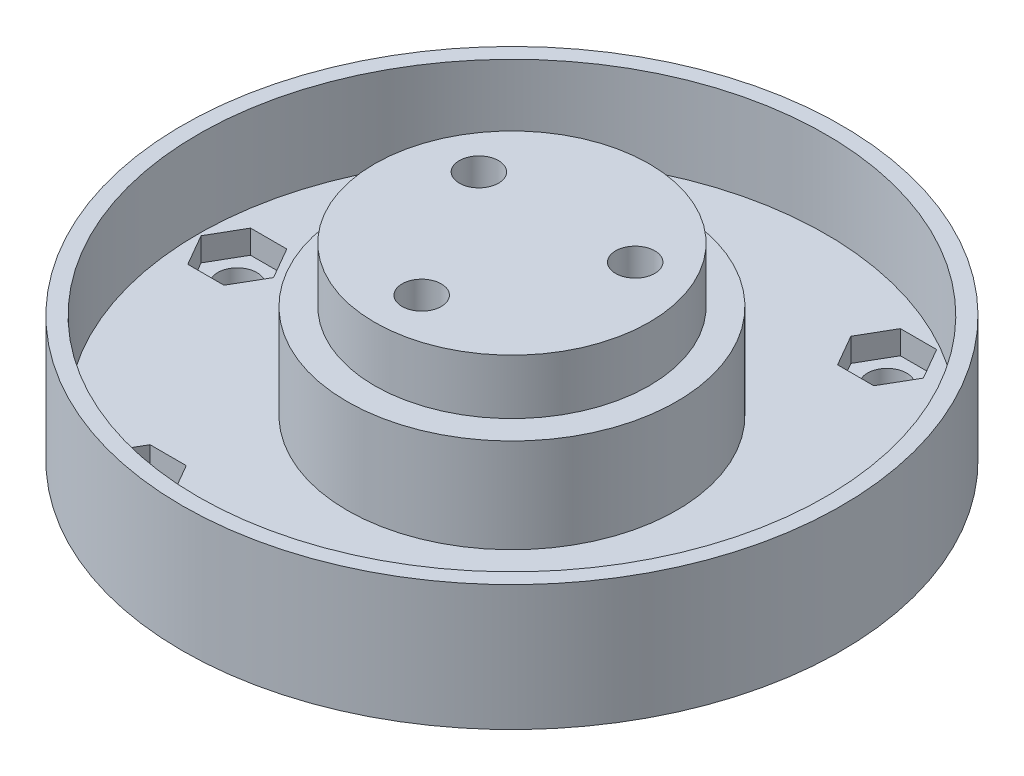
SolidWorks part; units mm, degrees
ref_plane "Front Plane" through (0, 0, 0) normal (0, 0, 1) x (1, 0, 0)
ref_plane "Top Plane" through (0, 0, 0) normal (0, 1, 0) x (1, 0, 0)
ref_plane "Right Plane" through (0, 0, 0) normal (1, 0, 0) x (0, 0, -1)
sketch "Sketch1" plane through (0, 0, 0) normal (0, 1, 0) x (1, 0, 0)
  line L0 (0, 0) -> (0, -11.5) construction
  line L1 (0, 0) -> (9.9593, 5.75) construction
  line L2 (0, 0) -> (-9.9593, 5.75) construction
  circle A0 centre (0, 0) radius 42
  circle A1 centre (0, 0) radius 21
  circle A2 centre (0, 0) radius 17.5
  circle A3 centre (0, 0) radius 40
  circle A4 centre (-9.9593, 5.75) radius 2.5
  circle A5 centre (9.9593, 5.75) radius 2.5
  circle A6 centre (0, -11.5) radius 2.5
  dimension "D1" = 35
  dimension "D2" = 42
  dimension "D3" = 2
  dimension "D6" = 5
  dimension "D8" = 80
  dimension "D4" = 120
  dimension "D5" = 120
  dimension "D7" = 11.5
extrude "Boss-Extrude1" add sketch "Sketch1" along normal blind 24 contours A2 region at (0, 0, 0)
extrude "Boss-Extrude2" add sketch "Sketch1<3>" along normal blind 17 contours A1 A2 region at (-20.406, 0, 0)
sketch "Sketch1<3>" plane through (0, 0, 0) normal (0, 1, 0) x (1, 0, 0) same geometry as "Sketch1"
extrude "Boss-Extrude4" add sketch "Sketch1<6>" along normal blind 5 contours A3 A1 region at (-38.8686, 0, 0)
sketch "Sketch1<6>" plane through (0, 0, 0) normal (0, 1, 0) x (1, 0, 0) same geometry as "Sketch1"
extrude "Boss-Extrude5" add sketch "Sketch1<7>" along normal blind 16 contours A0 A3 region at (-40.8121, 0, 0)
sketch "Sketch1<7>" plane through (0, 0, 0) normal (0, 1, 0) x (1, 0, 0) same geometry as "Sketch1"
sketch "Sketch2" plane through (0, 5, 0) normal (0, 1, 0) x (1, 0, 0)
  line L0 (0, 0) -> (-42, 0) construction
  circle A0 centre (0, 0) radius 30 construction
  circle A1 centre (0, 0) radius 35 construction
  circle A2 centre (-35, 0) radius 2.5
  circle A3 centre (-17.5, 30.3109) radius 2.5
  circle A4 centre (0, 0) radius 42 construction
  circle A5 centre (17.5, 30.3109) radius 2.5
  circle A6 centre (35, 0) radius 2.5
  circle A7 centre (17.5, -30.3109) radius 2.5
  circle A8 centre (-17.5, -30.3109) radius 2.5
  point P22 (0, 0)
  dimension "D1" = 60
  dimension "D2" = 5
  dimension "D3" = 5
  dimension "D4" = 6
extrude "Cut-Extrude1" cut sketch "Sketch2" against normal through all
sketch "Sketch3" plane through (0, 5, 0) normal (0, 1, 0) x (1, 0, 0)
  line L0 (0, 0) -> (0, 42) construction
  line L1 (-12.8812, 30.3109) -> (-15.1906, 34.3109)
  line L2 (-15.1906, 34.3109) -> (-19.8094, 34.3109)
  line L3 (-19.8094, 34.3109) -> (-22.1188, 30.3109)
  line L4 (-22.1188, 30.3109) -> (-19.8094, 26.3109)
  line L5 (-19.8094, 26.3109) -> (-15.1906, 26.3109)
  line L6 (-15.1906, 26.3109) -> (-12.8812, 30.3109)
  line L7 (0, 0) -> (36.3731, 21) construction
  line L8 (19.8094, 26.3109) -> (22.1188, 30.3109)
  line L9 (22.1188, 30.3109) -> (19.8094, 34.3109)
  line L10 (19.8094, 34.3109) -> (15.1906, 34.3109)
  line L11 (15.1906, 34.3109) -> (12.8812, 30.3109)
  line L12 (12.8812, 30.3109) -> (15.1906, 26.3109)
  line L13 (15.1906, 26.3109) -> (19.8094, 26.3109)
  line L14 (0, 0) -> (36.3731, -21) construction
  line L15 (32.6906, -4) -> (37.3094, -4)
  line L16 (37.3094, -4) -> (39.6188, 0)
  line L17 (39.6188, 0) -> (37.3094, 4)
  line L18 (37.3094, 4) -> (32.6906, 4)
  line L19 (32.6906, 4) -> (30.3812, 0)
  line L20 (30.3812, 0) -> (32.6906, -4)
  line L21 (0, 0) -> (0, -42) construction
  line L22 (12.8812, -30.3109) -> (15.1906, -34.3109)
  line L23 (15.1906, -34.3109) -> (19.8094, -34.3109)
  line L24 (19.8094, -34.3109) -> (22.1188, -30.3109)
  line L25 (22.1188, -30.3109) -> (19.8094, -26.3109)
  line L26 (19.8094, -26.3109) -> (15.1906, -26.3109)
  line L27 (15.1906, -26.3109) -> (12.8812, -30.3109)
  line L28 (0, 0) -> (-36.3731, -21) construction
  line L29 (-19.8094, -26.3109) -> (-22.1188, -30.3109)
  line L30 (-22.1188, -30.3109) -> (-19.8094, -34.3109)
  line L31 (-19.8094, -34.3109) -> (-15.1906, -34.3109)
  line L32 (-15.1906, -34.3109) -> (-12.8812, -30.3109)
  line L33 (-12.8812, -30.3109) -> (-15.1906, -26.3109)
  line L34 (-15.1906, -26.3109) -> (-19.8094, -26.3109)
  line L35 (0, 0) -> (-36.3731, 21) construction
  line L36 (-32.6906, 4) -> (-37.3094, 4)
  line L37 (-37.3094, 4) -> (-39.6188, 0)
  line L38 (-39.6188, 0) -> (-37.3094, -4)
  line L39 (-37.3094, -4) -> (-32.6906, -4)
  line L40 (-32.6906, -4) -> (-30.3812, 0)
  line L41 (-30.3812, 0) -> (-32.6906, 4)
  circle A0 centre (-17.5, 30.3109) radius 4 construction
  circle A1 centre (0, 0) radius 42 construction
  point P51 (0, 0)
  dimension "D1" = 8
  dimension "D2" = 6
extrude "Cut-Extrude2" cut sketch "Sketch3" against normal blind 3
